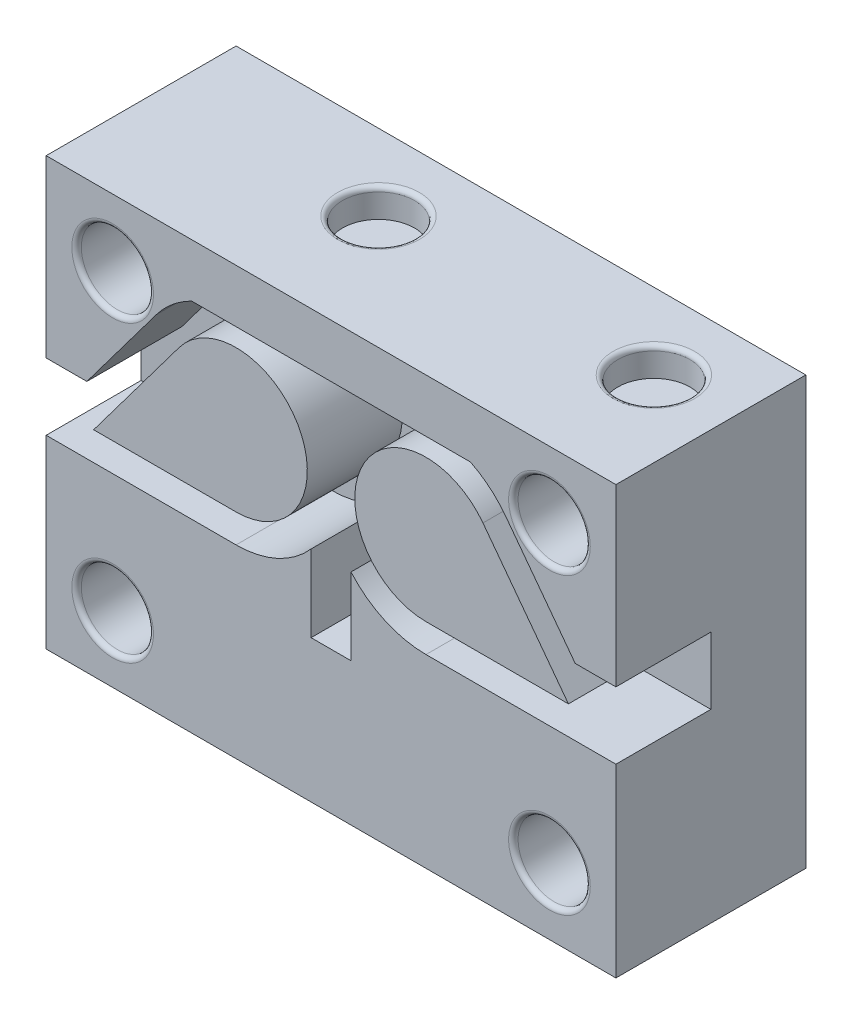
SolidWorks part; units mm, degrees
ref_plane "Front Plane" through (0, 0, 0) normal (0, 0, 1) x (1, 0, 0)
ref_plane "Top Plane" through (0, 0, 0) normal (0, 1, 0) x (1, 0, 0)
ref_plane "Right Plane" through (0, 0, 0) normal (1, 0, 0) x (0, 0, -1)
sketch "Sketch2" plane through (0, 0, 0) normal (0, 0, 1) x (1, 0, 0)
  line L0 (-37.3657, 7.5) -> (34.9105, 7.5) construction
  line L1 (-90, -22.5) -> (30, -22.5)
  line L2 (-30, -22.5) -> (-30, 22.5)
  line L3 (-30, 22.5) -> (30, 22.5)
  line L4 (30, -22.5) -> (30, 22.5)
  line L5 (-30, -22.5) -> (30, 22.5) construction
  line L6 (-30, 22.5) -> (30, -22.5) construction
  line L7 (-10, 29.4537) -> (-10, -35.1207) construction
  line L8 (0, 22.5) -> (0, -27.0967) construction
  line L9 (-10, 0) -> (-25, 0)
  line L10 (-25, 0) -> (-16, 12)
  line L11 (25, 0) -> (16, 12)
  line L12 (10, 0) -> (25, 0)
  line L13 (-57.8994, -3) -> (-2.1006, -3)
  line L14 (2.1, -16.875) -> (30, -16.875)
  line L15 (2.1006, 0.5827) -> (2.1, -16.875)
  line L16 (30, -16.875) -> (30, -3)
  line L17 (10, -3) -> (30, -3)
  line L18 (-10, -3) -> (-50, -3)
  line L19 (-2.1006, 0.5827) -> (-2.1006, -7.5128)
  line L20 (-2.1006, -7.5128) -> (2.1003, -7.5128)
  line L21 (-34.2857, 4.0476) -> (-25.7143, 4.0476)
  line L22 (-9.0554, -4.0054) -> (-5.1006, -4.0054)
  line L23 (-9.0554, -4.0054) -> (-9.0554, -10.0054)
  line L24 (-9.0554, -10.0054) -> (-5.1006, -10.0054)
  line L25 (-5.1006, -4.0054) -> (-5.1006, -10.0054)
  line L26 (2.1001, -14.3606) -> (-3.3999, -14.3606)
  line L27 (2.1001, -14.3606) -> (2.1001, -16.875)
  line L28 (2.1001, -16.875) -> (-3.3999, -16.875)
  line L29 (-3.3999, -14.3606) -> (-3.3999, -16.875)
  line L30 (-25.7143, 4.0476) -> (-18.4, 13.8)
  line L31 (-14.6784, 22.5) -> (-14.6784, 16.9001)
  line L32 (30, 4.0476) -> (25.7143, 4.0476)
  line L33 (25.7143, 4.0476) -> (18.4, 13.8)
  line L34 (14.6784, 22.5) -> (14.6784, 16.9001)
  line L35 (-60, 22.5) -> (-60, -27.0967) construction
  line L36 (-30, 22.5) -> (-90, -22.5) construction
  line L37 (-30, -22.5) -> (-90, 22.5) construction
  line L38 (-74.6784, 22.5) -> (-74.6784, 16.9001)
  line L39 (-85.7143, 4.0476) -> (-78.4, 13.8)
  line L40 (-90, 4.0476) -> (-85.7143, 4.0476)
  line L41 (-45.3216, 22.5) -> (-45.3216, 16.9001)
  line L42 (-34.2857, 4.0476) -> (-41.6, 13.8)
  line L43 (-56.6001, -14.3606) -> (-56.6001, -16.875)
  line L44 (-62.1001, -16.875) -> (-56.6001, -16.875)
  line L45 (-62.1001, -14.3606) -> (-62.1001, -16.875)
  line L46 (-62.1001, -14.3606) -> (-56.6001, -14.3606)
  line L47 (-54.8994, -4.0054) -> (-54.8994, -10.0054)
  line L48 (-50.9446, -10.0054) -> (-54.8994, -10.0054)
  line L49 (-50.9446, -4.0054) -> (-50.9446, -10.0054)
  line L50 (-50.9446, -4.0054) -> (-54.8994, -4.0054)
  line L51 (-57.8994, -7.5128) -> (-62.1003, -7.5128)
  line L52 (-57.8994, 0.5827) -> (-57.8994, -7.5128)
  line L53 (-70, -3) -> (-90, -3)
  line L54 (-90, -16.875) -> (-90, -3)
  line L55 (-62.1006, 0.5827) -> (-62.1, -16.875)
  line L56 (-62.1, -16.875) -> (-90, -16.875)
  line L57 (-70, 0) -> (-85, 0)
  line L58 (-85, 0) -> (-76, 12)
  line L59 (-35, 0) -> (-44, 12)
  line L60 (-50, 0) -> (-35, 0)
  line L61 (-90, -22.5) -> (-90, 22.5)
  line L62 (-30, 22.5) -> (-90, 22.5)
  line L63 (-74.6784, 16.9001) -> (-45.3216, 16.9001)
  circle A0 centre (-10, 7.5) radius 7.5
  circle A1 centre (10, 7.5) radius 7.5
  arc A2 (2.1006, 0.5827) -> (10, -3) centre (10, 7.5) ccw
  arc A3 (-2.1006, 0.5827) -> (-10, -3) centre (-10, 7.5) cw
  arc A4 (-18.4, 13.8) -> (-14.6784, 16.9001) centre (-10, 7.5) cw
  arc A5 (18.4, 13.8) -> (14.6784, 16.9001) centre (10, 7.5) ccw
  arc A6 (-78.4, 13.8) -> (-74.6784, 16.9001) centre (-70, 7.5) cw
  arc A7 (-41.6, 13.8) -> (-45.3216, 16.9001) centre (-50, 7.5) ccw
  arc A8 (-57.8994, 0.5827) -> (-50, -3) centre (-50, 7.5) ccw
  arc A9 (-62.1006, 0.5827) -> (-70, -3) centre (-70, 7.5) cw
  circle A10 centre (-70, 7.5) radius 7.5
  circle A11 centre (-50, 7.5) radius 7.5
  point P0 (0, 0)
  point P81 (-30, 4.0476)
  point P87 (-30, -3)
  point P93 (-60, 0)
  dimension "D5" = 15
  dimension "D8" = 10.5
  dimension "D24" = 15.3216
  dimension "D1" = 60
  dimension "D2" = 45
  dimension "D3" = 15
  dimension "D4" = 20
  dimension "D6" = 15
  dimension "D7" = 3
  dimension "D9" = 5.625
  dimension "D10" = 17.4577
  dimension "D11" = 27.9
  dimension "D12" = 4.2009
  dimension "D13" = 5.5
  dimension "D14" = 2.5144
  dimension "D15" = 3.9548
  dimension "D16" = 6
  dimension "D17" = 3
  dimension "D18" = 1.0054
  dimension "D19" = 5.625
  dimension "D20" = 3
  dimension "D21" = 10.5
  dimension "D23" = 4.2857
extrude "Boss-Extrude19" add sketch "Sketch2" along normal blind 20 contours A11 | L59 A11 L60 | A10 | A10 L58 L57 | L39 A6 L38 L62 L61 L40 | A7 L42 L21 L2 L62 L41 | L61 L1 L2 L13 L52 L51 L55 L46 L43 L44 L56 L50 L49 L48 L47 | L49 L50 L47 L48 | L55 A9 L53 L54 L56 L45 | L38 L63 L41 L62 | A8 L52 L13 | L46 L43 L44 L45 region at (-51.69, -14.5775, 0) region at (-75.7859, -9.7627, 0) region at (-36.1597, 15.038, 0) region at (-55.9983, -1.9661, 0) region at (-83.8403, 15.038, 0) region at (-60, 19.7001, 0) region at (-52.922, -7.0054, 0) region at (-78.9601, 3.02, 0) region at (-70, 7.5, 0) region at (-41.0399, 3.02, 0) region at (-50, 7.5, 0)
extrude "Boss-Extrude20" add sketch "Sketch2<27>" along normal blind 10 contours A9 L55 L51 L52 A8 L13 L2 L21 L42 A7 L63 A6 L39 L40 L61 L53 A10 L57 L58 L60 A11 L59 region at (-60, 4.9915, 0)
sketch "Sketch2<27>" plane through (0, 0, 0) normal (0, 0, 1) x (1, 0, 0) same geometry as "Sketch2"
sketch "Sketch3" plane through (0, 0, 20) normal (0, 0, 1) x (1, 0, 0)
  line L0 (-90, 15.5) -> (-30, 15.5) construction
  line L1 (-90, 4.0476) -> (-90, 22.5) construction
  line L2 (-30, 4.0476) -> (-30, 22.5) construction
  line L3 (-83, 22.5) -> (-83, -22.5) construction
  line L4 (-30, 22.5) -> (-90, 22.5) construction
  line L5 (-90, -22.5) -> (-30, -22.5) construction
  line L6 (-60, 22.5) -> (-60, -22.5) construction
  line L7 (-60, 0) -> (-90, 0) construction
  line L8 (-90, -3) -> (-90, 4.0476) construction
  line L9 (-60, 0) -> (-30, 0) construction
  line L10 (-30, -3) -> (-30, 4.0476) construction
  circle A0 centre (-83, 15.5) radius 3.8
  circle A1 centre (-37, 15.5) radius 3.8
  circle A2 centre (-37, -15.5) radius 3.8
  circle A3 centre (-83, -15.5) radius 3.8
  dimension "D3" = 7.6
  dimension "D1" = 7
  dimension "D2" = 7
extrude "Cut-Extrude1" cut sketch "Sketch3" against normal through all
fillet "Fillet1" radius 0.5 8 edges at (-86.8, -15.5, 0) (-79.2, 15.5, 0) (-33.2, -15.5, 0) (-40.8, 15.5, 0) (-86.8, -15.5, 20) (-33.2, -15.5, 20) (-40.8, 15.5, 20) (-79.2, 15.5, 20)
sketch "Sketch4" plane through (0, 22.5, 0) normal (0, 1, 0) x (1, 0, 0)
  line L2 (-30, -20) -> (-30, 0) construction
  line L3 (-30, 0) -> (-90, 0) construction
  circle A2 centre (-38, -8) radius 3.8
  circle A3 centre (-67, -8) radius 3.8
  dimension "D4" = 7.6
  dimension "D5" = 8
  dimension "D3" = 7.6
  dimension "D1" = 8
  dimension "D2" = 8
  dimension "D6" = 29
extrude "Cut-Extrude2" cut sketch "Sketch4" against normal blind 3
fillet "Fillet3" radius 0.5 2 edges at (-41.8, 22.5, 8) (-70.8, 22.5, 8)
sketch "Sketch5" plane through (0, -22.5, 0) normal (0, -1, 0) x (1, 0, 0)
  line L0 (-90, 20) -> (-90, 0) construction
  line L1 (-30, 0) -> (-90, 0) construction
  line L2 (-60, 20) -> (-60, 0) construction
  line L3 (-90, 20) -> (-30, 20) construction
  line L4 (-90, 0) -> (-30, 0) construction
  circle A0 centre (-75, 9) radius 3.925
  circle A1 centre (-45, 9) radius 3.925
  dimension "D3" = 7.85
  dimension "D1" = 15
  dimension "D2" = 9
extrude "Cut-Extrude3" cut sketch "Sketch5" against normal blind 3
fillet "Fillet4" radius 0.5 2 edges at (-45, -22.5, 12.925) (-75, -22.5, 5.075)
equation "\"W\"= 60mm"
equation "\"H\"= 45mm"
equation "\"dh\"= 1 / 3 * \"H\""
equation "\"dw\"= 1 / 3 * \"W\""
equation "\"r\"= 15mm"
equation "\"b\"= 3mm"
equation "\"r2\"= \"r\" / 2 + \"b\""
equation "\"bhg\"= 1 / 8 * \"H\""
equation "\"bwg\"= \"W\" / 2 - 2.1"
equation "\"t1\"= 10mm"
equation "\"t2\"= 30mm"
equation "\"t3\"= 40mm"
equation "\"t4\"= 50mm"
equation "\"D1\"= 50 - \"t2\""
equation "\"D1\"= 50 - \"t3\""
equation "\"D1\"= 50 - \"t1\""
equation "\"hftd\"= 5"
equation "\"hfdb\"= 8"
equation "\"hfth\"= 8'\""
equation "\"hftdb2\"= 29"
